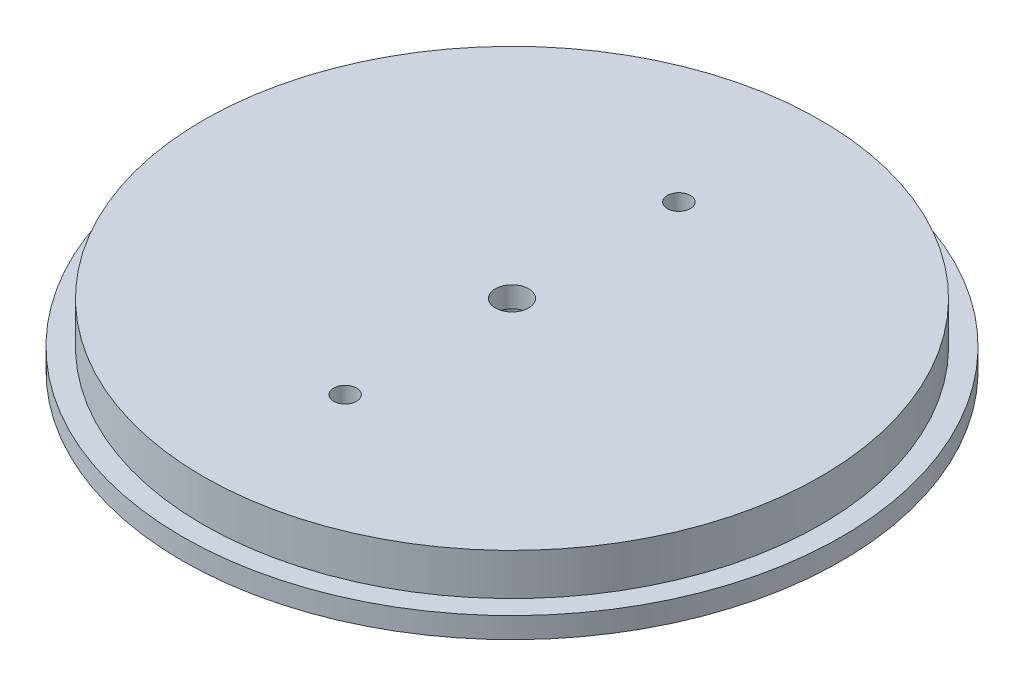
SolidWorks part; units mm, degrees
ref_plane "Front Plane" through (0, 0, 0) normal (0, 0, 1) x (1, 0, 0)
ref_plane "Top Plane" through (0, 0, 0) normal (0, 1, 0) x (1, 0, 0)
ref_plane "Right Plane" through (0, 0, 0) normal (1, 0, 0) x (0, 0, -1)
sketch "Sketch1" plane through (0, 0, 0) normal (0, 1, 0) x (1, 0, 0)
  circle A0 centre (0, 0) radius 79
  dimension "D1" = 158
extrude "Boss-Extrude1" add sketch "Sketch1" along normal blind 5
sketch "Sketch2" plane through (0, 5, 0) normal (0, 1, 0) x (1, 0, 0)
  circle A0 centre (0, 0) radius 74
  dimension "D1" = 148
extrude "Boss-Extrude2" add sketch "Sketch2" along normal blind 10
sketch "Sketch3" plane through (0, 15, 0) normal (0, 1, 0) x (1, 0, 0)
  line L0 (0, 0) -> (0, 40) construction
  line L1 (0, 0) -> (0, -40) construction
  circle A0 centre (0, 40) radius 2.75
  circle A1 centre (0, -40) radius 2.75
  dimension "D3" = 5.5
  dimension "D4" = 5.5
  dimension "D1" = 40
  dimension "D2" = 40
extrude "Cut-Extrude1" cut sketch "Sketch3" against normal through all
sketch "Sketch4" plane through (0, 15, 0) normal (0, 1, 0) x (1, 0, 0)
  circle A0 centre (0, 0) radius 4
  dimension "D1" = 8
extrude "Cut-Extrude2" cut sketch "Sketch4" against normal blind 5
sketch "Sketch5" plane through (0, 0, 0) normal (0, -1, 0) x (1, 0, 0)
  circle A0 centre (0, 0) radius 6
  dimension "D1" = 12
extrude "Cut-Extrude3" cut sketch "Sketch5" against normal blind 10
